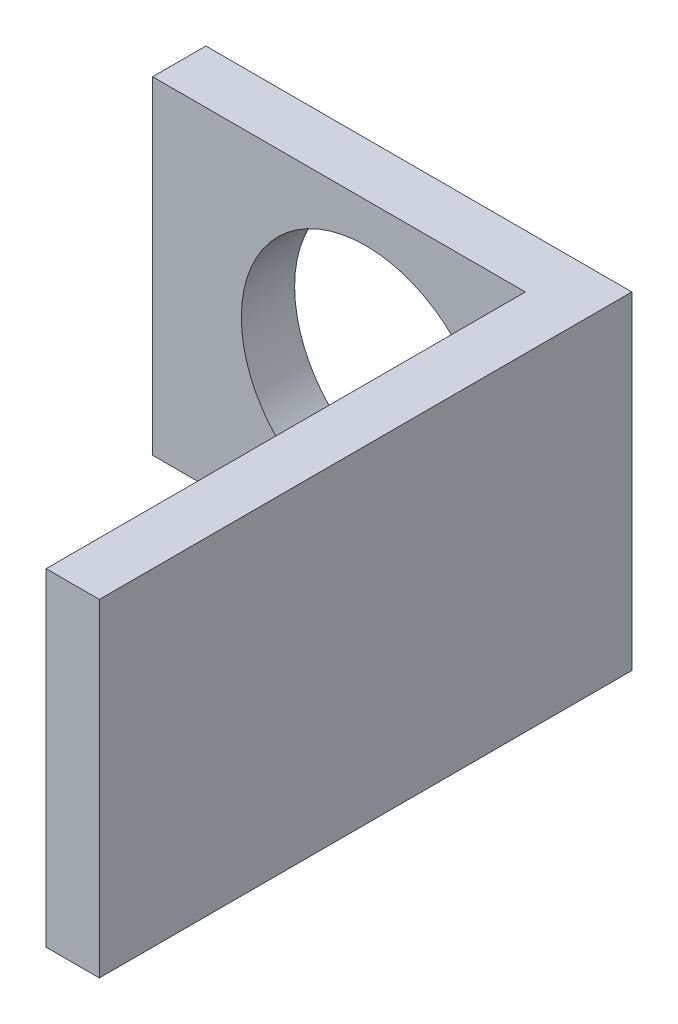
SolidWorks part; units mm, degrees
ref_plane "Front Plane" through (0, 0, 0) normal (0, 0, 1) x (1, 0, 0)
ref_plane "Top Plane" through (0, 0, 0) normal (0, 1, 0) x (1, 0, 0)
ref_plane "Right Plane" through (0, 0, 0) normal (1, 0, 0) x (0, 0, -1)
sketch "Sketch1" plane through (0, 0, 0) normal (0, 0, 1) x (1, 0, 0)
  line L0 (4.5, 4.6177) -> (4.5, -4.6177)
  line L1 (-6, -4.6177) -> (6, -4.6177)
  line L2 (-6, -4.6177) -> (-6, 4.6177)
  line L3 (-6, 4.6177) -> (6, 4.6177)
  line L4 (6, -4.6177) -> (6, 4.6177)
  line L5 (-6, -4.6177) -> (6, 4.6177) construction
  line L6 (-6, 4.6177) -> (6, -4.6177) construction
  circle A0 centre (0, 0) radius 3.5
  dimension "D1" = 7
  dimension "D2" = 12
  dimension "D3" = 1.5
extrude "Boss-Extrude1" add sketch "Sketch1" along normal blind 1.5 contours L3 L2 L1 L0 A0 region at (4.3602, 0, 0)
extrude "Boss-Extrude2" add sketch "Sketch1<3>" along normal blind 15 contours L1 L4 L3 L0 region at (5.25, 0, 0)
sketch "Sketch1<3>" plane through (0, 0, 0) normal (0, 0, 1) x (1, 0, 0) same geometry as "Sketch1"
